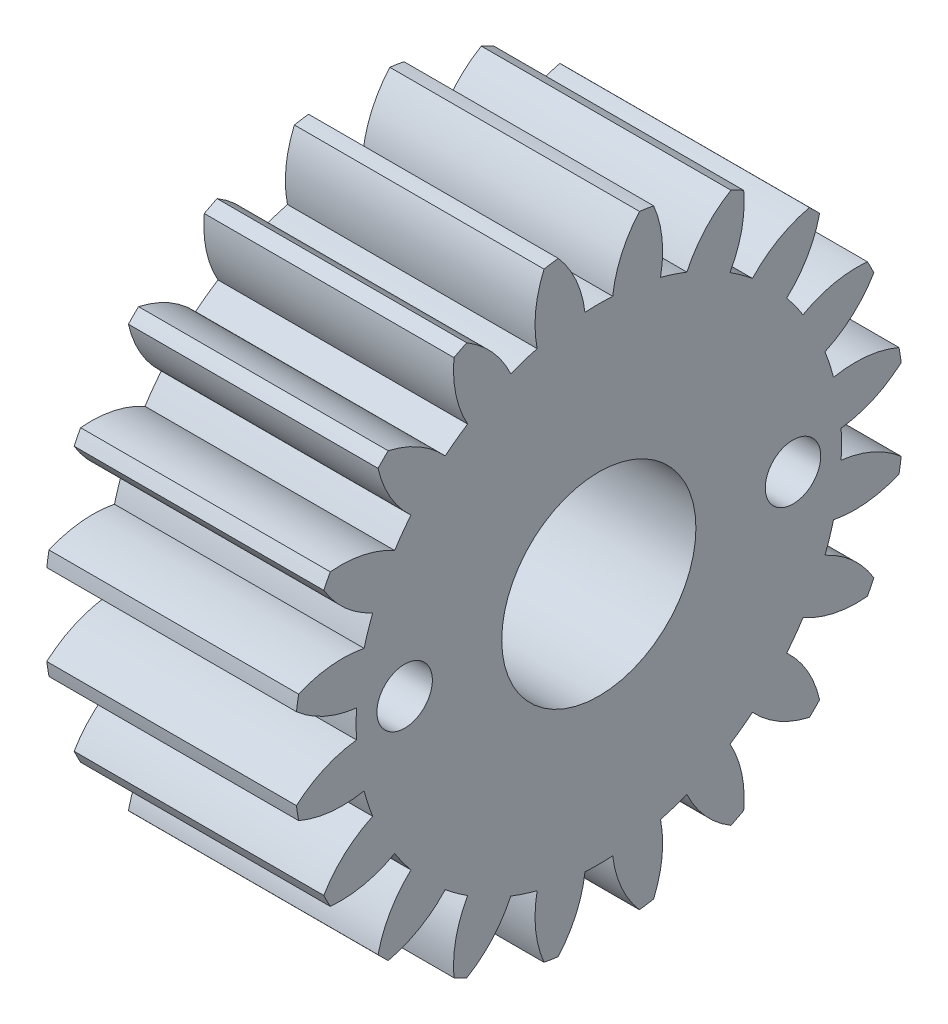
SolidWorks part; units mm, degrees
ref_plane "Plane1" through (0, 0, 0) normal (0, 0, 1) x (1, 0, 0)
ref_plane "Plane2" through (0, 0, 0) normal (0, 1, 0) x (1, 0, 0)
ref_plane "Plane3" through (0, 0, 0) normal (1, 0, 0) x (0, 0, -1)
other "Configuration Table"
sketch "HoldingSke" plane through (0, 0, 0) normal (0, 1, 0) x (1, 0, 0)
  line L0 (0, 0) -> (0.9397, -0.342)
  line L1 (-15, 0) -> (100, 0) construction
  line L2 (0, 0) -> (-2.1039, 2.3779)
  line L3 (0, 0) -> (-11.863, 4.5341)
  line L4 (0, 0) -> (8.1152, 2.9537)
  line L5 (0, 0) -> (-46.8476, -17.4728)
  line L6 (0, 0) -> (-4.1448, -2.7965)
  line L7 (-2.1039, 2.3779) -> (8.6586, 51.2059)
  line L8 (-76.2, 54.61) -> (-74.8, 54.61)
  line L9 (-71.009, 38.7566) -> (-53.1078, 45.2721)
  line L10 (-76.2, 71.12) -> (104.1128, 71.12)
  line L11 (0, 0) -> (-5, 0)
  line L12 (-76.2, 101.6) -> (-76.162, 101.6)
  line L13 (24.9733, 27.94) -> (52.9518, 28.4284)
  line L14 (24.9733, 27.94) -> (24.9743, 27.94)
  line L15 (24.9733, 27.94) -> (100.4006, 29.5858)
  line L16 (-63.627, -1) -> (-12.827, -1)
  circle A0 centre (0, 0) radius 4
  circle A1 centre (0, 0) radius 8.749
  circle A2 centre (0, 0) radius 37.5
  circle A3 centre (0, 0) radius 4
  dimension "Num_teeth" = 20
  dimension "Pitch_radius" = 180.3128
  dimension "Width" = 5
sketch "BasProSke" plane through (0, 0, 0) normal (0, 1, 0) x (1, 0, 0)
  line L0 (-10, 0) -> (60, 0) construction
  line L1 (0, 0) -> (0, 11)
  line L2 (0, 0) -> (9, 0)
  line L3 (9, 0) -> (9, 11)
  line L4 (9, 11) -> (0, 11)
  dimension "Thickness" = 9
  dimension "Diameter" = 22
revolve "Base-Revolve" add sketch "BasProSke" angle 360 about L0
sketch "TooCutSke" plane through (0, 0, 0) normal (1, 0, 0) x (0, 0, -1)
  line L1 (0, 0) -> (0, 107) construction
  line L2 (0, 0) -> (-0.8511, 9.9637) construction
  line L3 (0, 0) -> (-3.1206, 19.7028) construction
  line L4 (-0.8511, 9.9637) -> (-1.5603, 9.8514) construction
  arc A0 (0.4999, 8.7347) -> (-0.4999, 8.7347) centre (0, 0) ccw
  arc A1 (1.4852, 10.9249) -> (-1.4852, 10.9249) centre (0, 0) ccw
  circle A2 centre (0, 0) radius 10 construction
  circle A3 centre (0, 0) radius 9.3969 construction
  arc A4 (-0.4999, 8.7347) -> (-1.4852, 10.9249) centre (-4.4722, 8.2645) ccw
  arc A5 (1.4852, 10.9249) -> (0.4999, 8.7347) centre (4.4722, 8.2645) ccw
extrude "ToothCut" cut sketch "TooCutSke" along normal through all
fillet "Breaks" [suppressed] radius 0.02 tangent propagation no
fillet "RootFillets" [suppressed] radius 0.251
pattern_circular "TeethCuts" count 20 every 18 about axis through (-10, 0, 0) along (1, 0, 0) of "ToothCut", "RootFillets", "Breaks"
sketch "HubNeaOneSke" plane through (0, 0, 0) normal (-1, 0, 0) x (0, 0, 1)
  circle A0 centre (0, 0) radius 8.749
  dimension "Diameter" = 17.498
extrude "HubNearOne" [suppressed] add sketch "HubNeaOneSke" along normal blind 41.0001
sketch "HubNeaBotSke" plane through (0, 0, 0) normal (-1, 0, 0) x (0, 0, 1)
  circle A0 centre (0, 0) radius 8.749
  dimension "Diameter" = 17.498
extrude "HubNearBoth" [suppressed] add sketch "HubNeaBotSke" along normal blind 20.5
ref_plane "FarPln" through (9, 0, 0) normal (1, 0, 0) x (0, 0, -1)
sketch "HubFarSke" plane through (9, 0, 0) normal (1, 0, 0) x (0, 0, -1)
  circle A0 centre (0, 0) radius 8.749
  dimension "Diameter" = 17.498
extrude "HubFar" [suppressed] add sketch "HubFarSke" along normal blind 20.5
sketch "BorSke" plane through (0, 0, 0) normal (1, 0, 0) x (0, 0, -1)
  circle A0 centre (0, 0) radius 3.5
  dimension "Diameter" = 7
extrude "Bore" cut sketch "BorSke" along normal mid plane 100.0001
sketch "KeySke" plane through (0, 0, 0) normal (1, 0, 0) x (0, 0, -1)
  line L0 (-1.5, 0) -> (-1.5, 5.4)
  line L1 (-1.5, 5.4) -> (1.5, 5.4)
  line L2 (1.5, 5.4) -> (1.5, 0)
  line L3 (0, 0) -> (0, 34) construction
  line L4 (-1.5, 0) -> (1.5, 0)
  dimension "Width" = 3
extrude "Keyway" [suppressed] cut sketch "KeySke" along normal mid plane 100.0001
pattern_circular "Keyway2" [suppressed] count 2 every 90 about axis through (-10, 0, 0) along (1, 0, 0) reverse direction yes
sketch "Sketch1" plane through (9, 0, 0) normal (1, 0, 0) x (0, 0, -1)
  line L0 (-7, 0) -> (7, 0) construction
  circle A0 centre (-7, 0) radius 1
  circle A1 centre (7, 0) radius 1
  point P5 (0, 0)
  dimension "D1" = 2
  dimension "D2" = 2
extrude "Cut-Extrude1" cut sketch "Sketch1" against normal through all
equation "' \"Module@HoldingSke\" = 6.35"
equation "' \"Num_teeth@HoldingSke\" = 12"
equation "' \"Ap@HoldingSke\" =  20"
equation "' \"Ap@HoldingSke\" = 20"
equation "' \"Width@HoldingSke\" = 0.5 * 25.4"
equation "' \"Hub_dia@HoldingSke\"= 1 * 25.4"
equation "' \"Hub_dia@HoldingSke\" = 1 * 25.4"
equation "' \"Overall_len@HoldingSke\" = 1.0 * 25.4"
equation "' \"Bore@HoldingSke\" = 0.75 * 25.4"
equation "' \"T_dim@HoldingSke\" = 0.1 * 25.4"
equation "' \"Width@KeySke\" = 0.25 * 25.4"
equation "' \"Show_teeth@HoldingSke\" = 13"
equation "' \"Backlash@HoldingSke\" = 0.009 * 25.4"
equation "' \"Addendum_fac@HoldingSke\" = 1.0"
equation "' \"Dedendum_fac@HoldingSke\" = 1.25"
equation "' \"Dedendum_add@HoldingSke\" = 0.00005 * 25.4"
equation "' \"Clearance_fac@HoldingSke\" = 0.25"
equation "\"Pitch@HoldingSke\" = 1 / \"Module@HoldingSke\""
equation "\"Overcut_dia@TooCutSke\" = (\"Num_teeth@HoldingSke\" + 2 * \"Addendum_fac@HoldingSke\") / \"Pitch@HoldingSke\" + 0.002 * 25.4"
equation "\"Pitch_dia@TooCutSke\" = \"Num_teeth@HoldingSke\" / \"Pitch@HoldingSke\""
equation "\"Base_dia@TooCutSke\" = \"Num_teeth@HoldingSke\" / \"Pitch@HoldingSke\" * cos((\"Ap@HoldingSke\"  * 3.14159265 / 180))"
equation "\"Root_dia@TooCutSke\" = (\"Num_teeth@HoldingSke\" + 2) / \"Pitch@HoldingSke\" - 2 * (\"Addendum_fac@HoldingSke\" + \"Dedendum_fac@HoldingSke\") / \"Pitch@HoldingSke\" - \"Dedendum_add@HoldingSke\" * 2"
equation "\"Half_ang@TooCutSke\" = 180 / \"Num_teeth@HoldingSke\""
equation "\"Half_CT@TooCutSke\" = \"Num_teeth@HoldingSke\" / \"Pitch@HoldingSke\" * sin((3.14159265 / 2 / \"Num_teeth@HoldingSke\")) / 2 - 7 * \"Backlash@HoldingSke\" / 4"
equation "\"Flank_rad@TooCutSke\" = \"Num_teeth@HoldingSke\" / \"Pitch@HoldingSke\" / 5"
equation "\"Radius@RootFillets\" = \"Clearance_fac@HoldingSke\" / \"Pitch@HoldingSke\" + \"Dedendum_add@HoldingSke\""
equation "\"Break_rad@Breaks\" = 0.02 / \"Pitch@HoldingSke\""
equation "\"Thickness@HoldingSke\" = \"Width@HoldingSke\""
equation "\"OAL@HoldingSke\" = \"Thickness@HoldingSke\""
equation "\"MHD@HoldingSke\" = (\"Num_teeth@HoldingSke\" + 2) / \"Pitch@HoldingSke\" - 2 * (\"Addendum_fac@HoldingSke\" + \"Dedendum_fac@HoldingSke\")  / \"Pitch@HoldingSke\" - \"Dedendum_add@HoldingSke\" * 2"
equation "\"MBD@HoldingSke\" = (\"Num_teeth@HoldingSke\" + 2) / \"Pitch@HoldingSke\" - 2 * (\"Addendum_fac@HoldingSke\" + \"Dedendum_fac@HoldingSke\")  / \"Pitch@HoldingSke\" - \"Dedendum_add@HoldingSke\" * 2 - 0.002 * 25.4"
equation "\"MHD@HoldingSke\" = ((sgn( \"MHD@HoldingSke\" - \"Hub_dia@HoldingSke\" )-1)*( \"MHD@HoldingSke\" - \"Hub_dia@HoldingSke\" ))/-2+ \"Hub_dia@HoldingSke\""
equation "\"MBD@HoldingSke\" = ((sgn( \"MBD@HoldingSke\" - \"Bore@HoldingSke\" )-1)*( \"MBD@HoldingSke\" - \"Bore@HoldingSke\" ))/-2+ \"Bore@HoldingSke\""
equation "\"OAL@HoldingSke\" = ((sgn( \"OAL@HoldingSke\" - \"Overall_len@HoldingSke\" )+1)*( \"OAL@HoldingSke\" - \"Overall_len@HoldingSke\" ))/2 + \"Overall_len@HoldingSke\" + 0.000002 * 25.4"
equation "\"Num_teeth@TeethCuts\" = int( \"Show_teeth@HoldingSke\" ) + 1"
equation "\"Num_teeth@TeethCuts\" = ((sgn( \"Num_teeth@TeethCuts\" - \"Num_teeth@HoldingSke\" )-1)*( \"Num_teeth@TeethCuts\" - \"Num_teeth@HoldingSke\" ))/-2+ \"Num_teeth@HoldingSke\""
equation "\"Num_teeth@TeethCuts\" = ((sgn( \"Num_teeth@TeethCuts\" - 2.0)+1)*( \"Num_teeth@TeethCuts\" - 2.0))/2 +2.0"
equation "\"Angle@TeethCuts\" = 360.0 / \"Num_teeth@HoldingSke\""
equation "\"Diameter@BasProSke\" = (\"Num_teeth@HoldingSke\" + 2 * \"Addendum_fac@HoldingSke\") / \"Pitch@HoldingSke\""
equation "' \"Fillet_rad@BasProSke\" =  \"Thickness@HoldingSke\" * 0.05"
equation "' \"Fillet_rad@BasProSke\" = \"Thickness@HoldingSke\" * 0.05"
equation "\"MHD@HoldingSke\" = ((sgn( \"MHD@HoldingSke\" - \"Root_dia@TooCutSke\" )-1)*( \"MHD@HoldingSke\" - \"Root_dia@TooCutSke\" ))/-2+ \"Root_dia@TooCutSke\""
equation "\"Diameter@HubNeaOneSke\" = \"MHD@HoldingSke\""
equation "\"Length@HubNearOne\" = \"OAL@HoldingSke\" - \"Thickness@BasProSke\""
equation "\"Diameter@HubNeaBotSke\" = \"MHD@HoldingSke\""
equation "\"Length@HubNearBoth\" = ( \"OAL@HoldingSke\" - \"Thickness@BasProSke\" ) / 2.0"
equation "\"Thickness@FarPln\" = \"Thickness@BasProSke\""
equation "\"Diameter@HubFarSke\" = \"MHD@HoldingSke\""
equation "\"Length@HubFar\" = ( \"OAL@HoldingSke\" - \"Thickness@BasProSke\" ) / 2.0"
equation "\"D1@Bore\" = \"OAL@HoldingSke\" * 2.0"
equation "\"D1@Keyway\" = \"OAL@HoldingSke\" * 2.0"
equation "\"Offset@KeySke\" = \"T_dim@HoldingSke\" + \"MBD@HoldingSke\" / 2.0"
